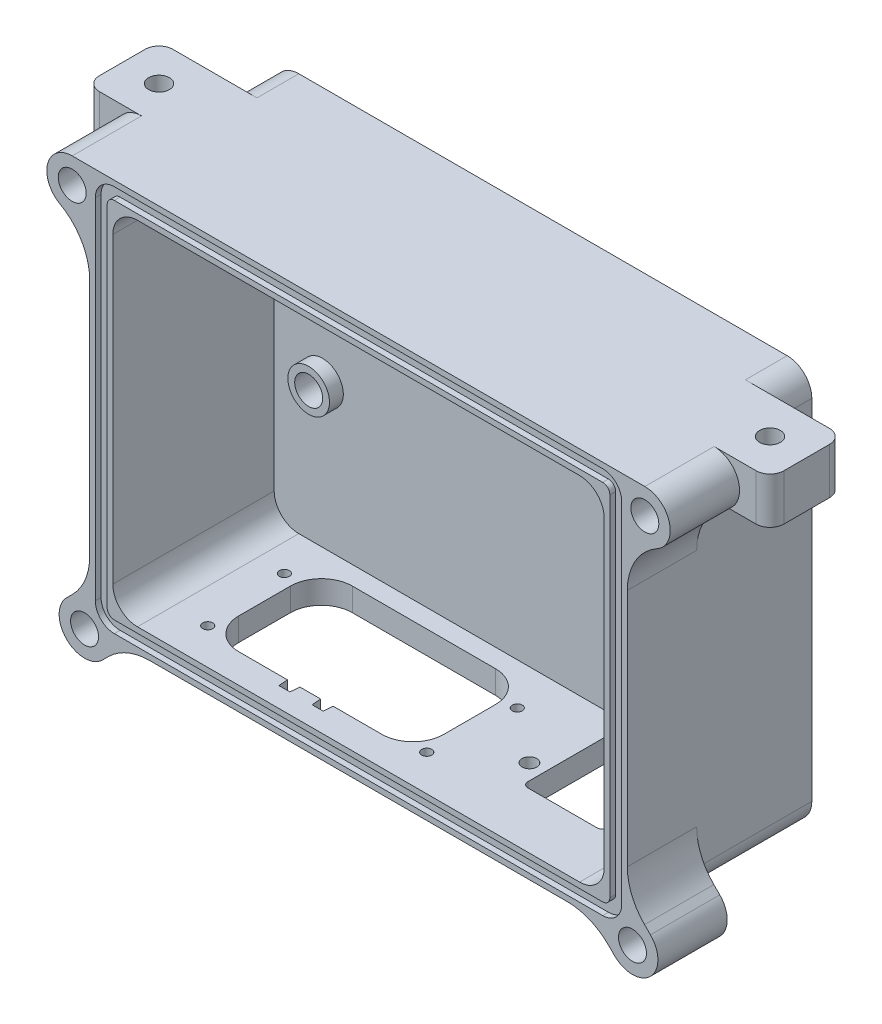
SolidWorks part; units mm, degrees
material "ABS"
ref_plane "X-Y Datum" through (0, 0, 0) normal (0, 0, 1) x (1, 0, 0)
ref_plane "X-Z Datum" through (0, 0, 0) normal (0, 1, 0) x (1, 0, 0)
ref_plane "Y-Z Datum" through (0, 0, 0) normal (1, 0, 0) x (0, 0, -1)
sketch "Sketch1" plane through (0, 0, 0) normal (0, 0, 1) x (1, 0, 0)
  line L1 (-53.1812, 38.1) -> (53.1812, 38.1)
  line L2 (-53.1812, 38.1) -> (-53.1812, -38.1)
  line L3 (-53.1812, -38.1) -> (53.1813, -38.1)
  line L4 (53.1812, 38.1) -> (53.1813, -38.1)
  line L5 (-53.1812, 38.1) -> (53.1813, -38.1) construction
  line L6 (-53.1812, -38.1) -> (53.1812, 38.1) construction
  point P0 (0, 0)
  dimension "D1" = 106.3625
  dimension "D2" = 76.2
extrude "Boss-Extrude1" add sketch "Sketch1" along normal blind 34.925
shell "Shell1" thickness 5 removed face at (0, 0, 34.925) outward yes
fillet "Fillet1" radius 5.334 8 edges at (-58.1812, -43.1, 14.9625) (58.1813, -43.1, 14.9625) (53.1812, 38.1, 17.4625) (58.1812, 43.1, 14.9625) (-58.1812, 43.1, 14.9625) (-53.1812, 38.1, 17.4625) (53.1813, -38.1, 17.4625) (-53.1812, -38.1, 17.4625)
sketch "Sketch2" plane through (0, 0, 34.925) normal (0, 0, 1) x (1, 0, 0)
  line L20 (-52.8472, -41.8827) -> (52.8473, -41.8827)
  line L21 (56.9639, -37.766) -> (56.9639, 37.766)
  line L22 (52.8472, 41.8827) -> (-52.8472, 41.8827)
  line L23 (-56.9639, 37.766) -> (-56.9639, -37.766)
  line L24 (-52.8472, -40.6) -> (52.8473, -40.6)
  line L25 (55.6812, -37.766) -> (55.6812, 37.766)
  line L26 (52.8472, 40.6) -> (-52.8472, 40.6)
  line L27 (-55.6812, 37.766) -> (-55.6812, -37.766)
  line L28 (-52.8472, -40.6) -> (52.8473, -40.6) construction
  line L29 (55.6812, -37.766) -> (55.6812, 37.766) construction
  line L30 (52.8472, 40.6) -> (-52.8472, 40.6) construction
  line L31 (-55.6812, 37.766) -> (-55.6812, -37.766) construction
  line L32 (-54.3986, 37.766) -> (-54.3986, -37.766)
  line L33 (-52.8472, -39.3173) -> (52.8473, -39.3173)
  line L34 (54.3986, -37.766) -> (54.3986, 37.766)
  line L35 (52.8472, 39.3173) -> (-52.8472, 39.3173)
  arc A16 (52.8473, -41.8827) -> (56.9639, -37.766) centre (52.8473, -37.766) ccw
  arc A17 (56.9639, 37.766) -> (52.8472, 41.8827) centre (52.8472, 37.766) ccw
  arc A18 (-52.8472, 41.8827) -> (-56.9639, 37.766) centre (-52.8472, 37.766) ccw
  arc A19 (-56.9639, -37.766) -> (-52.8472, -41.8827) centre (-52.8472, -37.766) ccw
  arc A20 (-55.6812, -37.766) -> (-52.8472, -40.6) centre (-52.8472, -37.766) ccw
  arc A21 (52.8473, -40.6) -> (55.6812, -37.766) centre (52.8473, -37.766) ccw
  arc A22 (55.6812, 37.766) -> (52.8472, 40.6) centre (52.8472, 37.766) ccw
  arc A23 (-52.8472, 40.6) -> (-55.6812, 37.766) centre (-52.8472, 37.766) ccw
  arc A24 (-55.6812, -37.766) -> (-52.8472, -40.6) centre (-52.8472, -37.766) ccw construction
  arc A25 (52.8473, -40.6) -> (55.6812, -37.766) centre (52.8473, -37.766) ccw construction
  arc A26 (55.6812, 37.766) -> (52.8472, 40.6) centre (52.8472, 37.766) ccw construction
  arc A27 (-52.8472, 40.6) -> (-55.6812, 37.766) centre (-52.8472, 37.766) ccw construction
  arc A28 (-52.8472, 39.3173) -> (-54.3986, 37.766) centre (-52.8472, 37.766) ccw
  arc A29 (-54.3986, -37.766) -> (-52.8472, -39.3173) centre (-52.8472, -37.766) ccw
  arc A30 (52.8473, -39.3173) -> (54.3986, -37.766) centre (52.8473, -37.766) ccw
  arc A31 (54.3986, 37.766) -> (52.8472, 39.3173) centre (52.8472, 37.766) ccw
  dimension "D4" = 2.5654
  dimension "D1" = 2.5
  dimension "D2" = 1.2827
  dimension "D3" = 1.2827
extrude "Cut-Extrude1" cut sketch "Sketch2" against normal blind 1.2446
sketch "Sketch4" plane through (0, 0, 34.925) normal (0, 0, 1) x (1, 0, 0)
  line L0 (56.9639, -37.766) -> (56.9639, 37.766) construction
  line L1 (52.8472, 43.1) -> (-52.8472, 43.1) construction
  line L2 (61.9639, 43.1) -> (52.8472, 43.1)
  line L3 (61.9639, 32.1) -> (58.1812, 32.1)
  line L4 (58.1813, -37.766) -> (58.1812, 37.766) construction
  line L6 (47.8473, -32.766) -> (59.2937, -44.2125)
  line L7 (55.4046, -48.1016) -> (50.4031, -43.1)
  line L8 (-52.8472, -43.1) -> (52.8473, -43.1) construction
  line L9 (63.1828, -40.3234) -> (58.1812, -35.3218)
  line L10 (-52.8472, -43.1) -> (52.8473, -43.1)
  line L11 (58.1813, -37.766) -> (58.1812, 37.766)
  circle A0 centre (61.9639, 37.6) radius 3.025
  circle A1 centre (61.9639, 37.6) radius 5.5
  arc A2 (47.8473, -38.1) -> (53.1813, -32.766) centre (47.8473, -32.766) ccw construction
  circle A3 centre (59.2937, -44.2125) radius 3.025
  circle A4 centre (59.2937, -44.2125) radius 5.5
  arc A5 (52.8473, -41.8827) -> (56.9639, -37.766) centre (52.8473, -37.766) ccw construction
  arc A6 (52.8473, -43.1) -> (58.1813, -37.766) centre (52.8473, -37.766) ccw construction
  arc A7 (58.1812, 37.766) -> (52.8472, 43.1) centre (52.8472, 37.766) ccw construction
  arc A8 (52.8473, -43.1) -> (58.1813, -37.766) centre (52.8473, -37.766) ccw
  arc A9 (58.1812, 37.766) -> (52.8472, 43.1) centre (52.8472, 37.766) ccw
  point P14 (51.619, -36.5377)
  point P23 (55.7582, -40.6769)
  dimension "D1" = 6.05
  dimension "D2" = 11
  dimension "D3" = 5
  dimension "D4" = 5
extrude "Boss-Extrude2" add sketch "Sketch4" against normal blind 15 separate body contours A9 L11 A1 A0 | A9 A1 L2 | A0 | A8 A4 L9 L11 | A8 L10 L7 A4 | A8 A4 A3 | A3 | A1 L11 L3 region at (57.3854, 42.3955, 34.925) region at (59.5123, -37.7425, 34.925) region at (65.7474, 41.3835, 34.925) region at (59.099, 32.5392, 34.925) region at (60.4186, -41.4968, 34.925) region at (64.2313, -42.1673, 34.925) region at (52.8237, -44.431, 34.925) region at (61.9639, 37.6, 34.925)
sketch "Sketch5" plane through (0, 0, 34.925) normal (0, 0, 1) x (1, 0, 0)
  line L0 (61.9639, 32.1) -> (58.1812, 32.1) construction
  line L1 (61.9639, 43.1) -> (52.8472, 43.1) construction
  line L2 (58.1813, -37.766) -> (58.1812, 37.766) construction
  line L3 (-52.8472, -43.1) -> (52.8473, -43.1) construction
  line L4 (63.1828, -40.3234) -> (58.1812, -35.3218) construction
  line L5 (55.4046, -48.1016) -> (50.4031, -43.1) construction
  line L6 (47.8473, -32.766) -> (59.2937, -44.2125) construction
  line L7 (61.9639, 32.1) -> (58.1812, 32.1)
  line L8 (61.9639, 43.1) -> (52.8472, 43.1)
  line L9 (58.1813, -37.766) -> (58.1812, 37.766)
  line L10 (-52.8472, -43.1) -> (52.8473, -43.1)
  line L11 (63.1828, -40.3234) -> (58.1812, -35.3218)
  line L12 (55.4046, -48.1016) -> (50.4031, -43.1)
  line L13 (47.8473, -32.766) -> (59.2937, -44.2125)
  arc A0 (58.1812, 37.766) -> (52.8472, 43.1) centre (52.8472, 37.766) ccw construction
  circle A1 centre (59.2937, -44.2125) radius 3.025
  circle A2 centre (59.2937, -44.2125) radius 3.025
  circle A3 centre (61.9639, 37.6) radius 5.5
  circle A4 centre (61.9639, 37.6) radius 5.5
  circle A5 centre (61.9639, 37.6) radius 3.025
  circle A6 centre (61.9639, 37.6) radius 3.025
  circle A7 centre (59.2937, -44.2125) radius 5.5
  circle A8 centre (59.2937, -44.2125) radius 5.5
  arc A9 (52.8473, -43.1) -> (58.1813, -37.766) centre (52.8473, -37.766) ccw construction
  arc A10 (58.1812, 37.766) -> (52.8472, 43.1) centre (52.8472, 37.766) ccw
  arc A11 (52.8473, -43.1) -> (58.1813, -37.766) centre (52.8473, -37.766) ccw
  dimension "D1" = 0
  dimension "D2" = 0
  dimension "D3" = 0
  dimension "D4" = 0
extrude "Cut-Extrude4" cut sketch "Sketch5" against normal blind 8 contours A6 | A2 region at (60.4186, -41.4968, 34.925) region at (61.9639, 37.6, 34.925)
mirror "Mirror3" about plane through (0, 0, 0) normal (1, 0, 0) of bodies 107 106
combine bodies "Combine3" operation type add bodies to combine 102 107 106 109 110
fillet "Fillet2" radius 12.7 6 edges at (-58.1812, 32.1, 27.425) (-50.4031, -43.1, 27.425) (-58.1812, -35.3218, 27.425) (50.4031, -43.1, 27.425) (58.1812, -35.3218, 27.425) (58.1812, 32.1, 27.425)
sketch "Sketch6" plane through (0, 0, 0) normal (0, 0, 1) x (1, 0, 0)
  line L0 (-42.7107, -5.0748) -> (-42.7107, -9.2748) construction
  line L1 (-42.7107, 20.8332) -> (-42.7107, 16.6332) construction
  line L2 (29.0253, -6.1988) -> (29.0253, -10.3988) construction
  line L3 (29.0253, 21.7412) -> (29.0253, 17.5412) construction
  circle A0 centre (-42.7107, -7.1748) radius 3.025
  circle A1 centre (-42.7107, -7.1748) radius 4.5
  circle A2 centre (-42.7107, 18.7332) radius 3.025
  circle A3 centre (-42.7107, 18.7332) radius 4.5
  circle A4 centre (29.0253, -8.2988) radius 3.025
  circle A5 centre (29.0253, -8.2988) radius 4.5
  circle A6 centre (29.0253, 19.6412) radius 3.025
  circle A7 centre (29.0253, 19.6412) radius 4.5
  spline S0 degree 3 poles (29.0253, -6.1988) (24.8253, -6.1988) (24.8253, -10.3988) (29.0253, -10.3988) (33.2253, -10.3988) (33.2253, -6.1988) (29.0253, -6.1988) (24.8253, -6.1988) (24.8253, -10.3988) knots -0.5 0 0 0 0.5 0.5 0.5 1 1 1 1.5 1.5 1.5 weights 1 0.333333 0.333333 1 0.333333 0.333333 1 0.333333 0.333333 only from (29.0253, -6.1988) to (29.0253, -6.1988) construction
  spline S1 degree 3 poles (29.0253, 21.7412) (24.8253, 21.7412) (24.8253, 17.5412) (29.0253, 17.5412) (33.2253, 17.5412) (33.2253, 21.7412) (29.0253, 21.7412) (24.8253, 21.7412) (24.8253, 17.5412) knots -0.5 0 0 0 0.5 0.5 0.5 1 1 1 1.5 1.5 1.5 weights 1 0.333333 0.333333 1 0.333333 0.333333 1 0.333333 0.333333 only from (29.0253, 21.7412) to (29.0253, 21.7412) construction
  spline S2 degree 3 poles (-42.7107, 20.8332) (-46.9107, 20.8332) (-46.9107, 16.6332) (-42.7107, 16.6332) (-38.5107, 16.6332) (-38.5107, 20.8332) (-42.7107, 20.8332) (-46.9107, 20.8332) (-46.9107, 16.6332) knots -0.5 0 0 0 0.5 0.5 0.5 1 1 1 1.5 1.5 1.5 weights 1 0.333333 0.333333 1 0.333333 0.333333 1 0.333333 0.333333 only from (-42.7107, 20.8332) to (-42.7107, 20.8332) construction
  spline S3 degree 3 poles (-42.7107, -5.0748) (-46.9107, -5.0748) (-46.9107, -9.2748) (-42.7107, -9.2748) (-38.5107, -9.2748) (-38.5107, -5.0748) (-42.7107, -5.0748) (-46.9107, -5.0748) (-46.9107, -9.2748) knots -0.5 0 0 0 0.5 0.5 0.5 1 1 1 1.5 1.5 1.5 weights 1 0.333333 0.333333 1 0.333333 0.333333 1 0.333333 0.333333 only from (-42.7107, -5.0748) to (-42.7107, -5.0748) construction
  spline S4 degree 3 poles (29.0253, -6.1988) (24.8253, -6.1988) (24.8253, -10.3988) (29.0253, -10.3988) (33.2253, -10.3988) (33.2253, -6.1988) (29.0253, -6.1988) (24.8253, -6.1988) (24.8253, -10.3988) knots -0.5 0 0 0 0.5 0.5 0.5 1 1 1 1.5 1.5 1.5 weights 1 0.333333 0.333333 1 0.333333 0.333333 1 0.333333 0.333333 only from (29.0253, -6.1988) to (29.0253, -6.1988) construction
  spline S5 degree 3 poles (29.0253, 21.7412) (24.8253, 21.7412) (24.8253, 17.5412) (29.0253, 17.5412) (33.2253, 17.5412) (33.2253, 21.7412) (29.0253, 21.7412) (24.8253, 21.7412) (24.8253, 17.5412) knots -0.5 0 0 0 0.5 0.5 0.5 1 1 1 1.5 1.5 1.5 weights 1 0.333333 0.333333 1 0.333333 0.333333 1 0.333333 0.333333 only from (29.0253, 21.7412) to (29.0253, 21.7412) construction
  spline S6 degree 3 poles (-42.7107, 20.8332) (-46.9107, 20.8332) (-46.9107, 16.6332) (-42.7107, 16.6332) (-38.5107, 16.6332) (-38.5107, 20.8332) (-42.7107, 20.8332) (-46.9107, 20.8332) (-46.9107, 16.6332) knots -0.5 0 0 0 0.5 0.5 0.5 1 1 1 1.5 1.5 1.5 weights 1 0.333333 0.333333 1 0.333333 0.333333 1 0.333333 0.333333 only from (-42.7107, 20.8332) to (-42.7107, 20.8332) construction
  spline S7 degree 3 poles (-42.7107, -5.0748) (-46.9107, -5.0748) (-46.9107, -9.2748) (-42.7107, -9.2748) (-38.5107, -9.2748) (-38.5107, -5.0748) (-42.7107, -5.0748) (-46.9107, -5.0748) (-46.9107, -9.2748) knots -0.5 0 0 0 0.5 0.5 0.5 1 1 1 1.5 1.5 1.5 weights 1 0.333333 0.333333 1 0.333333 0.333333 1 0.333333 0.333333 only from (-42.7107, -5.0748) to (-42.7107, -5.0748) construction
  dimension "D1" = 6.05
  dimension "D2" = 9
extrude "Boss-Extrude3" add sketch "Sketch6" along normal blind 3 contours A5 A4 | A4 | A7 A6 | A6 | A0 | A1 A0 | A3 A2 region at (-42.7107, -7.1748, 0) region at (-47.0835, -7.1748, 0) region at (-47.0835, 18.7332, 0) region at (29.0253, -8.2988, 0) region at (24.6525, -8.2988, 0) region at (29.0253, 19.6412, 0) region at (24.6525, 19.6412, 0)
sketch "Sketch7" plane through (0, 0, 3) normal (0, 0, 1) x (1, 0, 0)
  circle A1 centre (29.0253, -8.2988) radius 4.5
  circle A2 centre (29.0253, -8.2988) radius 4.5
  circle A3 centre (29.0253, -8.2988) radius 3.025
  circle A4 centre (29.0253, -8.2988) radius 3.025
  circle A5 centre (-42.7107, 18.7332) radius 4.5
  circle A6 centre (-42.7107, 18.7332) radius 4.5
  circle A7 centre (-42.7107, 18.7332) radius 3.025
  circle A8 centre (-42.7107, 18.7332) radius 3.025
  circle A9 centre (-42.7107, -7.1748) radius 4.5
  circle A10 centre (-42.7107, -7.1748) radius 4.5
  circle A11 centre (-42.7107, -7.1748) radius 3.025
  circle A12 centre (-42.7107, -7.1748) radius 3.025
  circle A13 centre (29.0253, 19.6412) radius 4.5
  circle A14 centre (29.0253, 19.6412) radius 4.5
  circle A15 centre (29.0253, 19.6412) radius 3.025
  circle A16 centre (29.0253, 19.6412) radius 3.025
  dimension "D1" = 0
  dimension "D2" = 0
  dimension "D3" = 0
  dimension "D4" = 0
  dimension "D5" = 0
  dimension "D6" = 0
  dimension "D7" = 0
  dimension "D8" = 0
extrude "Cut-Extrude5" cut sketch "Sketch7" against normal blind 6 contours A8 | A12 | A16 | A4 region at (29.0253, -8.2988, 3) region at (-42.7107, 18.7332, 3) region at (-42.7107, -7.1748, 3) region at (29.0253, 19.6412, 3)
sketch "Sketch8" plane through (0, 43.1, 0) normal (0, 1, 0) x (1, 0, 0)
  line L0 (0, 5) -> (0, -34.925)
  line L2 (52.8472, 5) -> (-52.8472, 5) construction
  line L3 (61.9639, -34.925) -> (-61.9639, -34.925) construction
  line L4 (-61.9639, -19.925) -> (-52.8472, -19.925) construction
  line L5 (-74.0562, -19.925) -> (74.0562, -19.925)
  line L6 (-74.0562, -19.925) -> (-74.0562, -4.05)
  line L7 (-74.0562, -4.05) -> (74.0562, -4.05)
  line L8 (74.0562, -19.925) -> (74.0562, -4.05)
  line L9 (-74.0562, -19.925) -> (74.0562, -4.05) construction
  line L10 (-74.0562, -4.05) -> (74.0562, -19.925) construction
  line L11 (-58.1812, -19.925) -> (-58.1812, 5) construction
  line L12 (-58.1812, -19.925) -> (-58.1812, -4.05)
  line L13 (-74.0562, -19.925) -> (-58.1812, -4.05)
  line L14 (52.8472, -19.925) -> (52.8472, 5) construction
  line L15 (58.1812, 5) -> (58.1812, -19.925) construction
  line L16 (52.8472, -19.925) -> (52.8472, 5)
  line L17 (58.1812, 5) -> (58.1812, -19.925)
  line L18 (58.1812, -19.925) -> (74.0562, -4.05)
  circle A0 centre (-66.1187, -11.9875) radius 2
  circle A1 centre (66.1187, -11.9875) radius 2
  point P5 (0, -11.9875)
  line M8 (61.9639, -19.925) -> (52.8472, -19.925)
  dimension "D3" = 4
  dimension "D1" = 15.875
  dimension "D2" = 15.875
extrude "Boss-Extrude4" add sketch "Sketch8" against normal blind 10 contours A0 L13 L5 L12 | A0 L13 L7 L6 | L13 A0 | L13 A0 | A1 L18 L7 L17 | L18 A1 | L18 A1 | A1 L18 L5 L8 M8 region at (-68.8719, 43.1, 9.2343) region at (-63.3656, 43.1, 14.7407) region at (-65.5185, 43.1, 12.5877) region at (-66.719, 43.1, 11.3873) region at (63.3656, 43.1, 9.2343) region at (68.8719, 43.1, 14.7407) region at (65.5185, 43.1, 11.3873) region at (66.719, 43.1, 12.5877)
sketch "Sketch9" plane through (0, 43.1, 0) normal (0, 1, 0) x (1, 0, 0)
  line L0 (-58.1812, -19.925) -> (-58.1812, -4.05) construction
  line L1 (-74.0562, -19.925) -> (-58.1812, -4.05) construction
  line L2 (0, 5) -> (0, -34.925) construction
  line L3 (-74.0562, -19.925) -> (74.0562, -19.925) construction
  line L4 (74.0562, -19.925) -> (74.0562, -4.05) construction
  line L5 (-74.0562, -4.05) -> (74.0562, -4.05) construction
  line L6 (-74.0562, -19.925) -> (-74.0562, -4.05) construction
  line L7 (-58.1812, -19.925) -> (-58.1812, -4.05)
  line L8 (-74.0562, -19.925) -> (-58.1812, -4.05)
  line L9 (0, 5) -> (0, -34.925)
  line L10 (-74.0562, -19.925) -> (74.0562, -19.925)
  line L11 (74.0562, -19.925) -> (74.0562, -4.05)
  line L12 (-74.0562, -4.05) -> (74.0562, -4.05)
  line L13 (-74.0562, -19.925) -> (-74.0562, -4.05)
  line L14 (-52.8472, 5) -> (-52.8472, -19.925) construction
  line L15 (-52.8472, 5) -> (-52.8472, -19.925)
  line L16 (52.8472, -19.925) -> (52.8472, 5) construction
  line L17 (52.8472, -19.925) -> (52.8472, 5)
  circle A0 centre (-66.1187, -11.9875) radius 2 construction
  circle A1 centre (-66.1187, -11.9875) radius 2
  line M6 (-52.8472, 5) -> (-52.8472, -19.925)
  line M7 (-52.8472, -19.925) -> (-58.1812, -19.925)
  line M8 (-58.1812, -19.925) -> (-58.1812, -4.05)
extrude "Boss-Extrude5" add sketch "Sketch9" against normal up to surface contours L12 M8 M7 M6 region at (-55.5142, 43.1, 11.9875) up to face at (-56.4895, 40.3415, 6.78)
fillet "Fillet3" radius 3 4 edges at (-74.0562, 38.1, 19.925) (-74.0562, 38.1, 4.05) (74.0562, 38.1, 19.925) (74.0562, 38.1, 4.05)
sketch "Sketch12" plane through (0, 43.1, 0) normal (0, 1, 0) x (1, 0, 0)
  line L0 (52.8472, -19.925) -> (52.8472, 5) construction
  line L1 (-52.8472, 5) -> (-52.8472, -19.925) construction
  line L2 (-58.1812, -19.925) -> (-58.1812, -4.05) construction
  line L3 (-74.0562, -19.925) -> (-58.1812, -4.05) construction
  line L4 (-74.0562, -19.925) -> (74.0562, -19.925) construction
  line L5 (74.0562, -19.925) -> (74.0562, -4.05) construction
  line L6 (-74.0562, -4.05) -> (74.0562, -4.05) construction
  line L7 (-74.0562, -19.925) -> (-74.0562, -4.05) construction
  line L8 (0, 5) -> (0, -34.925) construction
  line L9 (52.8472, -19.925) -> (52.8472, 5)
  line L10 (-52.8472, 5) -> (-52.8472, -19.925)
  line L11 (-58.1812, -19.925) -> (-58.1812, -4.05)
  line L12 (-74.0562, -19.925) -> (-58.1812, -4.05)
  line L13 (-74.0562, -19.925) -> (74.0562, -19.925)
  line L14 (74.0562, -19.925) -> (74.0562, -4.05)
  line L15 (-74.0562, -4.05) -> (74.0562, -4.05)
  line L16 (-74.0562, -19.925) -> (-74.0562, -4.05)
  line L17 (0, 5) -> (0, -34.925)
  circle A1 centre (-66.1187, -11.9875) radius 2
  circle A2 centre (-66.1187, -11.9875) radius 2
  line M12 (58.1812, -4.05) -> (58.1812, -19.925)
  line M13 (58.1812, -19.925) -> (52.8472, -19.925)
  line M14 (52.8472, -19.925) -> (52.8472, 5)
  dimension "D1" = 0
extrude "Boss-Extrude6" add sketch "Sketch12" against normal up to surface (5.334 mm away) contours L15 M14 M13 M12 region at (55.5142, 43.1, 11.9875) up to face at (56.4895, 40.3415, 6.78)
hole_wizard "M4 Clearance Hole1" positions "Sketch10" profile "Sketch11" hole size "M4" standard "ANSI Metric" end condition through all
sketch "Sketch10" plane through (0, 33.1, 0) normal (0, -1, 0) x (-1, 0, 0)
  point P0 (66.1187, -11.9875)
  point P4 (-66.1187, -11.9875)
sketch "Sketch11" plane through (-66.1187, 33.1, 11.9875) normal (1, 0, 0) x (0, 0, -1)
  line L0 (0, 0) -> (0, 10)
  line L1 (0, 10) -> (2.25, 10)
  line L2 (2.25, 10) -> (2.25, 0)
  line L5 (2.25, 0) -> (0, 0)
  line L11 (0, -6.35) -> (0, 107.95) construction
  dimension "Thru Hole Dia." = 4.5
  dimension "Thru Hole Depth" = 10
sketch "Sketch13" plane through (0, -43.1, 0) normal (0, -1, 0) x (1, 0, 0)
  line L0 (-12.2307, 28.1302) -> (-12.4056, 30.1302) construction
  line L1 (-32.2307, 28.1302) -> (-21.2307, 28.1302) construction
  line L2 (-38.4307, 10.7302) -> (-38.4307, 21.9302) construction
  line L3 (-1.2307, 4.5302) -> (-32.2307, 4.5302) construction
  line L4 (4.9693, 21.9302) -> (4.9693, 10.7302) construction
  line L5 (-12.2307, 28.1302) -> (-1.2307, 28.1302) construction
  line L6 (-21.2307, 28.1302) -> (-21.0557, 30.1302) construction
  line L7 (-21.0557, 30.1302) -> (-19.6056, 30.1302) construction
  line L8 (-19.4307, 28.1302) -> (-19.6056, 30.1302) construction
  line L9 (-19.4307, 28.1302) -> (-14.0307, 28.1302) construction
  line L10 (-14.0307, 28.1302) -> (-13.8557, 30.1302) construction
  line L11 (-13.8557, 30.1302) -> (-12.4056, 30.1302) construction
  line L12 (-12.2307, 28.1302) -> (-12.4056, 30.1302) construction
  line L13 (-13.8557, 30.1302) -> (-12.4056, 30.1302) construction
  line L14 (-14.0307, 28.1302) -> (-13.8557, 30.1302) construction
  line L15 (-19.4307, 28.1302) -> (-14.0307, 28.1302) construction
  line L16 (-19.4307, 28.1302) -> (-19.6056, 30.1302) construction
  line L17 (-21.0557, 30.1302) -> (-19.6056, 30.1302) construction
  line L18 (-21.2307, 28.1302) -> (-21.0557, 30.1302) construction
  line L19 (-12.2307, 28.1302) -> (-1.2307, 28.1302) construction
  line L36 (4.9693, 21.9302) -> (4.9693, 10.7302) construction
  line L37 (-1.2307, 4.5302) -> (-32.2307, 4.5302) construction
  line L38 (-38.4307, 10.7302) -> (-38.4307, 21.9302) construction
  line L39 (-32.2307, 28.1302) -> (-21.2307, 28.1302) construction
  line L40 (-11.7725, 28.6302) -> (-11.9475, 30.6302)
  line L41 (-14.3138, 30.6302) -> (-11.9475, 30.6302)
  line L42 (-14.4888, 28.6302) -> (-14.3138, 30.6302)
  line L43 (-18.9725, 28.6302) -> (-14.4888, 28.6302)
  line L44 (-18.9725, 28.6302) -> (-19.1475, 30.6302)
  line L45 (-21.5138, 30.6302) -> (-19.1475, 30.6302)
  line L46 (-21.6888, 28.6302) -> (-21.5138, 30.6302)
  line L47 (-32.2307, 28.6302) -> (-21.6888, 28.6302)
  line L48 (-38.9307, 10.7302) -> (-38.9307, 21.9302)
  line L49 (-1.2307, 4.0302) -> (-32.2307, 4.0302)
  line L50 (5.4693, 21.9302) -> (5.4693, 10.7302)
  line L51 (-11.7725, 28.6302) -> (-1.2307, 28.6302)
  line L52 (40.1813, 21.725) -> (40.1813, 5.275) construction
  line L53 (39.5313, 4.625) -> (24.5813, 4.625) construction
  line L54 (23.9313, 5.275) -> (23.9313, 21.725) construction
  line L55 (24.5813, 22.375) -> (39.5313, 22.375) construction
  line L56 (40.1813, 21.725) -> (40.1813, 5.275) construction
  line L57 (39.5313, 4.625) -> (24.5813, 4.625) construction
  line L58 (23.9313, 5.275) -> (23.9313, 21.725) construction
  line L59 (24.5813, 22.375) -> (39.5313, 22.375) construction
  line L60 (45.1426, 34.925) -> (-45.1426, 34.925)
  line L61 (-45.1426, 34.925) -> (-45.1426, 19.925)
  line L62 (-45.1426, 19.925) -> (-52.8473, 19.925)
  line L63 (-52.8473, 19.925) -> (-52.8472, -5)
  line L64 (-52.8472, -5) -> (52.8473, -5)
  line L65 (52.8473, -5) -> (52.8473, 19.925)
  line L66 (52.8473, 19.925) -> (45.1426, 19.925)
  line L67 (45.1426, 19.925) -> (45.1426, 34.925)
  line L74 (52.8473, 19.925) -> (45.1426, 19.925)
  line L76 (40.6813, 21.725) -> (40.6813, 5.275)
  line L77 (39.5313, 4.125) -> (24.5813, 4.125)
  line L78 (23.4313, 5.275) -> (23.4313, 21.725)
  line L79 (24.5813, 22.875) -> (39.5313, 22.875)
  arc A0 (-32.2307, 28.1302) -> (-38.4307, 21.9302) centre (-32.2307, 21.9302) ccw construction
  arc A1 (-38.4307, 10.7302) -> (-32.2307, 4.5302) centre (-32.2307, 10.7302) ccw construction
  arc A2 (-1.2307, 4.5302) -> (4.9693, 10.7302) centre (-1.2307, 10.7302) ccw construction
  arc A3 (4.9693, 21.9302) -> (-1.2307, 28.1302) centre (-1.2307, 21.9302) ccw construction
  arc A4 (4.9693, 21.9302) -> (-1.2307, 28.1302) centre (-1.2307, 21.9302) ccw construction
  arc A5 (-1.2307, 4.5302) -> (4.9693, 10.7302) centre (-1.2307, 10.7302) ccw construction
  arc A6 (-38.4307, 10.7302) -> (-32.2307, 4.5302) centre (-32.2307, 10.7302) ccw construction
  arc A7 (-32.2307, 28.1302) -> (-38.4307, 21.9302) centre (-32.2307, 21.9302) ccw construction
  arc A8 (-32.2307, 28.6302) -> (-38.9307, 21.9302) centre (-32.2307, 21.9302) ccw
  arc A9 (-38.9307, 10.7302) -> (-32.2307, 4.0302) centre (-32.2307, 10.7302) ccw
  arc A10 (-1.2307, 4.0302) -> (5.4693, 10.7302) centre (-1.2307, 10.7302) ccw
  arc A11 (5.4693, 21.9302) -> (-1.2307, 28.6302) centre (-1.2307, 21.9302) ccw
  arc A12 (40.1813, 21.725) -> (39.5313, 22.375) centre (39.5313, 21.725) ccw construction
  arc A13 (39.5313, 4.625) -> (40.1813, 5.275) centre (39.5313, 5.275) ccw construction
  arc A14 (23.9313, 5.275) -> (24.5813, 4.625) centre (24.5813, 5.275) ccw construction
  arc A15 (24.5813, 22.375) -> (23.9313, 21.725) centre (24.5813, 21.725) ccw construction
  arc A16 (40.1813, 21.725) -> (39.5313, 22.375) centre (39.5313, 21.725) ccw construction
  arc A17 (39.5313, 4.625) -> (40.1813, 5.275) centre (39.5313, 5.275) ccw construction
  arc A18 (23.9313, 5.275) -> (24.5813, 4.625) centre (24.5813, 5.275) ccw construction
  arc A19 (24.5813, 22.375) -> (23.9313, 21.725) centre (24.5813, 21.725) ccw construction
  arc A20 (39.5313, 4.125) -> (40.6813, 5.275) centre (39.5313, 5.275) ccw
  arc A21 (23.4313, 5.275) -> (24.5813, 4.125) centre (24.5813, 5.275) ccw
  arc A22 (24.5813, 22.875) -> (23.4313, 21.725) centre (24.5813, 21.725) ccw
  arc A23 (40.6813, 21.725) -> (39.5313, 22.875) centre (39.5313, 21.725) ccw
  circle A24 centre (44.0563, 9) radius 1.6 construction
  circle A25 centre (20.0563, 18) radius 1.6 construction
  arc A26 (8.0543, 27.1302) -> (5.8843, 27.1302) centre (6.9693, 27.1302) ccw construction
  arc A27 (5.8843, 27.1302) -> (8.0543, 27.1302) centre (6.9693, 27.1302) ccw construction
  arc A28 (9.5543, 9.0302) -> (7.3843, 9.0302) centre (8.4693, 9.0302) ccw construction
  arc A29 (7.3843, 9.0302) -> (9.5543, 9.0302) centre (8.4693, 9.0302) ccw construction
  arc A30 (-40.8457, 9.0302) -> (-43.0157, 9.0302) centre (-41.9307, 9.0302) ccw construction
  arc A31 (-43.0157, 9.0302) -> (-40.8457, 9.0302) centre (-41.9307, 9.0302) ccw construction
  arc A32 (-39.3457, 27.1302) -> (-41.5157, 27.1302) centre (-40.4307, 27.1302) ccw construction
  arc A33 (-41.5157, 27.1302) -> (-39.3457, 27.1302) centre (-40.4307, 27.1302) ccw construction
  circle A34 centre (44.0563, 9) radius 1.6
  circle A35 centre (20.0563, 18) radius 1.6
  arc A36 (8.0543, 27.1302) -> (5.8843, 27.1302) centre (6.9693, 27.1302) ccw
  arc A37 (5.8843, 27.1302) -> (8.0543, 27.1302) centre (6.9693, 27.1302) ccw
  arc A38 (9.5543, 9.0302) -> (7.3843, 9.0302) centre (8.4693, 9.0302) ccw
  arc A39 (7.3843, 9.0302) -> (9.5543, 9.0302) centre (8.4693, 9.0302) ccw
  arc A40 (-40.8457, 9.0302) -> (-43.0157, 9.0302) centre (-41.9307, 9.0302) ccw
  arc A41 (-43.0157, 9.0302) -> (-40.8457, 9.0302) centre (-41.9307, 9.0302) ccw
  arc A42 (-39.3457, 27.1302) -> (-41.5157, 27.1302) centre (-40.4307, 27.1302) ccw
  arc A43 (-41.5157, 27.1302) -> (-39.3457, 27.1302) centre (-40.4307, 27.1302) ccw
  dimension "D1" = 0.5
  dimension "D2" = 0
  dimension "D3" = 0.5
extrude "Cut-Extrude6" cut sketch "Sketch13" against normal blind 5 contours L50 A11 L51 L40 L41 L42 L43 L44 L45 L46 L47 A8 L48 A9 L49 A10 | L76 A23 L79 A22 L78 A21 L77 A20 | A42 A43 | A40 A41 | A38 A39 | A36 A37 | A35 | A34 region at (-16.7307, -43.1, 16.4571) region at (32.0563, -43.1, 13.5) region at (44.0563, -43.1, 9) region at (20.0563, -43.1, 18) region at (6.9693, -43.1, 27.1302) region at (8.4693, -43.1, 9.0302) region at (-41.9307, -43.1, 9.0302) region at (-40.4307, -43.1, 27.1302)
